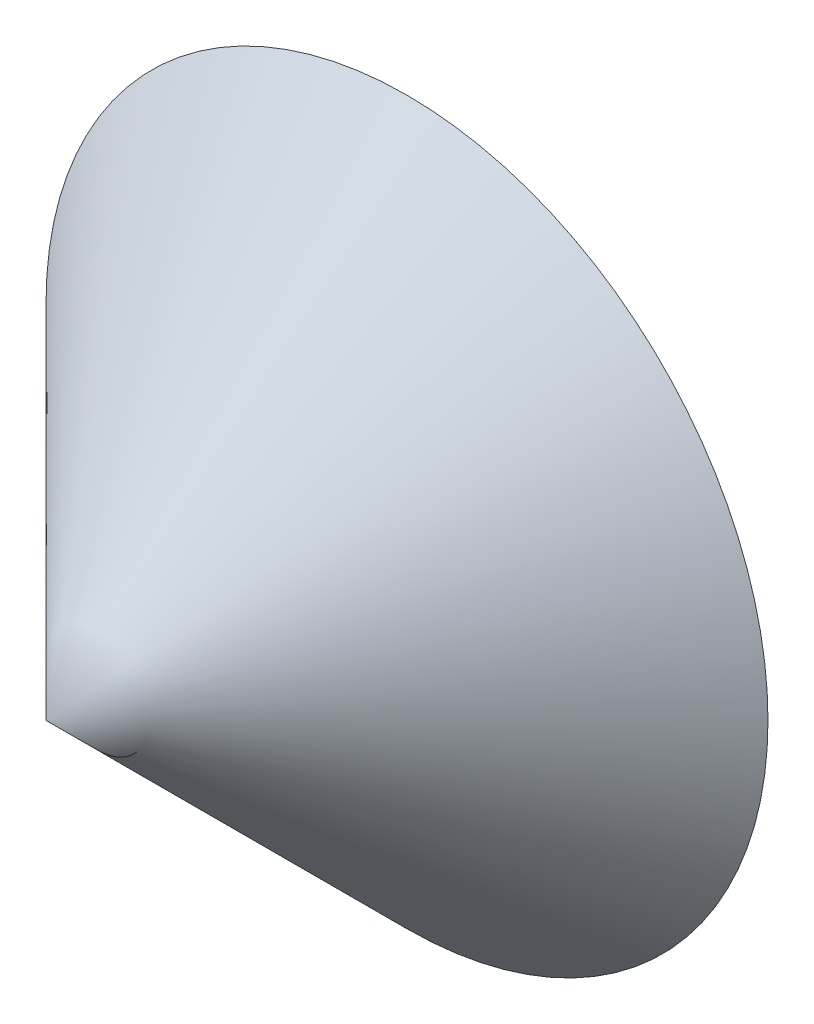
SolidWorks part; units mm, degrees
ref_plane "Front Plane" through (0, 0, 0) normal (0, 0, 1) x (1, 0, 0)
ref_plane "Top Plane" through (0, 0, 0) normal (0, 1, 0) x (1, 0, 0)
ref_plane "Right Plane" through (0, 0, 0) normal (1, 0, 0) x (0, 0, -1)
sketch "Sketch1" plane through (0, 0, 0) normal (0, 0, 1) x (1, 0, 0)
  line L0 (-5.4991, 5.1) -> (5.4991, 5.1)
  circle A0 centre (0, 0) radius 50
  circle A1 centre (0, 0) radius 15
  arc A2 (-5.4991, 5.1) -> (5.4991, 5.1) centre (0, 0) ccw
  circle A3 centre (0, 0) radius 50
  dimension "D1" = 15
  dimension "D2" = 30
  dimension "D3" = 100
  dimension "D4" = 5.1
extrude "Boss-Extrude1" add sketch "Sketch1" against normal blind 2 contours A1 A2 L0 region at (-14.5757, 0, 0)
ref_plane "Plane1" through (0, 0, 50) normal (0, 0, 1) x (1, 0, 0)
sketch "Sketch2" plane through (0, 0, 50) normal (0, 0, 1) x (1, 0, 0)
  point P0 (0, 0)
sketch "Sketch3" plane through (0, 0, 0) normal (0, 0, 1) x (1, 0, 0)
  circle A0 centre (0, 0) radius 50
  dimension "D1" = 100
loft "Loft2" add profiles "Sketch3", "Sketch2"
extrude "Cut-Extrude1" cut sketch "Sketch1<4>" along normal blind 10 contours L0 A2 region at (0, -0.6996, 0)
sketch "Sketch1<4>" plane through (0, 0, 0) normal (0, 0, 1) x (1, 0, 0) same geometry as "Sketch1"
